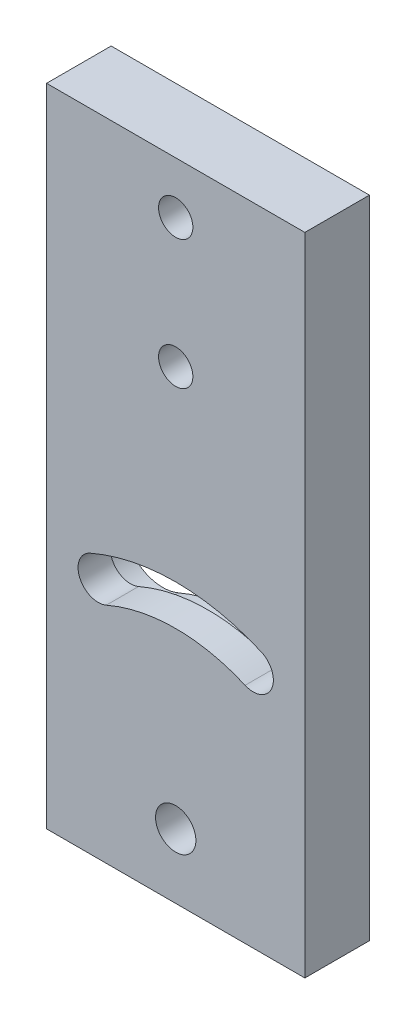
SolidWorks part; units mm, degrees
ref_plane "Front Plane" through (0, 0, 0) normal (0, 0, 1) x (1, 0, 0)
ref_plane "Top Plane" through (0, 0, 0) normal (0, 1, 0) x (1, 0, 0)
ref_plane "Right Plane" through (0, 0, 0) normal (1, 0, 0) x (0, 0, -1)
sketch "Sketch1" plane through (0, 0, 0) normal (0, 0, 1) x (1, 0, 0)
  line L1 (0, 0) -> (50.8, 0)
  line L2 (0, 0) -> (0, 127)
  line L3 (0, 127) -> (50.8, 127)
  line L4 (50.8, 0) -> (50.8, 127)
  circle A0 centre (25.4, 12.7) radius 3.9687
  circle A6 centre (25.4, 116.84) radius 3.3734
  circle A7 centre (25.4, 91.44) radius 3.3734
  arc A8 (42.2275, 51.2566) -> (8.5725, 51.2566) centre (25.4, 12.7) ccw
  arc A9 (39.0525, 43.9818) -> (11.7475, 43.9818) centre (25.4, 12.7) ccw
  arc A10 (8.5725, 51.2566) -> (11.7475, 43.9818) centre (10.16, 47.6192) ccw
  arc A11 (39.0525, 43.9818) -> (42.2275, 51.2566) centre (40.64, 47.6192) ccw
  arc A12 (43.7515, 54.7486) -> (7.0485, 54.7486) centre (25.4, 12.7) ccw
  arc A13 (7.0485, 54.7486) -> (13.2715, 40.4899) centre (10.16, 47.6192) ccw
  arc A14 (37.5285, 40.4899) -> (13.2715, 40.4899) centre (25.4, 12.7) ccw
  arc A15 (37.5285, 40.4899) -> (43.7515, 54.7486) centre (40.64, 47.6192) ccw
  dimension "D3" = 7.9375
  dimension "D6" = 6.7469
  dimension "D7" = 7.9375
  dimension "D8" = 7.9375
  dimension "D9" = 6.7469
  dimension "D13" = 84.1375
  dimension "D14" = 68.2625
  dimension "D1" = 127
  dimension "D2" = 50.8
  dimension "D4" = 25.4
  dimension "D5" = 12.7
  dimension "D10" = 10.16
  dimension "D11" = 10.16
  dimension "D12" = 25.4
  dimension "D15" = 10.16
  dimension "D17" = 25.4
  dimension "D18" = 0
  dimension "D16" = 3.81
extrude "Boss-Extrude2" add sketch "Sketch1" along normal blind 12.7 contours L2 L1 L4 L3 | A11 A8 A10 A9 | A7 | A6 | A0
extrude "Cut-Extrude1" cut sketch "Sketch1<3>" along normal blind 6.35 from surface contours A14 A15 A12 A13 A11 A9 A10 A8 region at (47.3138, 44.7065, 0) starting at face at (25.4, 48.4159, 0)
sketch "Sketch1<3>" plane through (0, 0, 0) normal (0, 0, 1) x (1, 0, 0) same geometry as "Sketch1"
sketch "Sketch3" plane through (0, 0, 0) normal (0, 0, -1) x (-1, 0, 0)
  circle A0 centre (-25.4, 116.84) radius 5.5562
  circle A1 centre (-25.4, 91.44) radius 5.5562
  dimension "D1" = 11.1125
  dimension "D2" = 11.1125
extrude "Cut-Extrude2" cut sketch "Sketch3" against normal blind 6.35 from surface starting at face at (25.4, 47.6539, 0)
sketch "Sketch4" plane through (0, 0, 12.7) normal (0, 0, 1) x (1, 0, 0)
  circle A0 centre (25.4, 12.7) radius 7.62
  dimension "D1" = 15.24
extrude "Cut-Extrude3" cut sketch "Sketch4" along normal blind 6.35 from surface starting at face at (30.9562, 116.84, 0)
